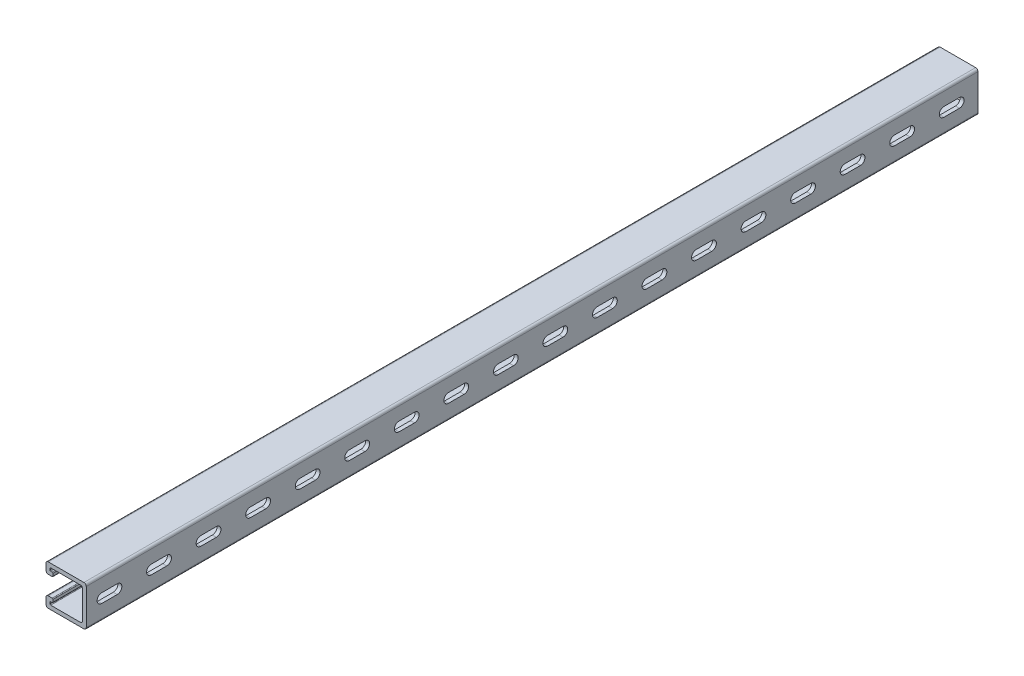
SolidWorks part; units mm, degrees
ref_plane "Front Plane" through (0, 0, 0) normal (0, 0, 1) x (1, 0, 0)
ref_plane "Top Plane" through (0, 0, 0) normal (0, 1, 0) x (1, 0, 0)
ref_plane "Right Plane" through (0, 0, 0) normal (1, 0, 0) x (0, 0, -1)
sketch "Sketch1" plane through (0, 0, 0) normal (0, 0, 1) x (1, 0, 0)
  line L0 (-13.5255, 9.525) -> (-18.2499, 9.525)
  line L1 (-20.6375, 11.9126) -> (-20.6375, 18.2499)
  line L2 (-18.2499, 20.6375) -> (18.2499, 20.6375)
  line L3 (20.6375, 18.2499) -> (20.6375, -18.2499)
  line L4 (18.2499, -20.6375) -> (-18.2499, -20.6375)
  line L5 (-20.6375, -18.2499) -> (-20.6375, -11.9126)
  line L6 (-18.2499, -9.525) -> (-13.5255, -9.525)
  line L7 (0, 0) -> (20.6375, 0) construction
  line L8 (0, 0) -> (0, 20.6375) construction
  arc A0 (-20.6375, 18.2499) -> (-18.2499, 20.6375) centre (-18.2499, 18.2499) cw
  arc A1 (-18.2499, 9.525) -> (-20.6375, 11.9126) centre (-18.2499, 11.9126) cw
  arc A2 (-20.6375, -11.9126) -> (-18.2499, -9.525) centre (-18.2499, -11.9126) cw
  arc A3 (-18.2499, -20.6375) -> (-20.6375, -18.2499) centre (-18.2499, -18.2499) cw
  arc A4 (20.6375, -18.2499) -> (18.2499, -20.6375) centre (18.2499, -18.2499) cw
  arc A5 (18.2499, 20.6375) -> (20.6375, 18.2499) centre (18.2499, 18.2499) cw
  point P14 (-20.6375, 20.6375)
  point P23 (20.6375, -20.6375)
  point P26 (20.6375, 20.6375)
  dimension "D4" = 2.3876
  dimension "D1" = 41.275
  dimension "D2" = 41.275
  dimension "D3" = 19.05
  dimension "D5" = 7.112
extrude "Extrude-Thin1" add sketch "Sketch1" against normal blind 914.4 thin thin type one direction wall 4.064
fillet "Fillet2" radius 0.762 8 edges at (-16.5735, 13.589, -457.2) (-16.5735, -16.5735, -457.2) (-16.5735, 16.5735, -457.2) (-13.5255, 13.589, -457.2) (-13.5255, 9.525, -457.2) (-13.5255, -9.525, -457.2) (-13.5255, -13.589, -457.2) (-16.5735, -13.589, -457.2)
fillet "Fillet3" radius 1.524 2 edges at (16.5735, 16.5735, -457.2) (16.5735, -16.5735, -457.2)
sketch "Sketch2" plane through (20.6375, 0, 0) normal (1, 0, 0) x (0, 0, -1)
  line L0 (15.875, 0) -> (31.75, 0) construction
  line L1 (15.875, 4.7625) -> (31.75, 4.7625)
  line L2 (15.875, -4.7625) -> (31.75, -4.7625)
  line L4 (15.875, 0) -> (0, 0) construction
  line L5 (23.8125, 0) -> (74.6125, 0) construction
  line L6 (0, 18.2499) -> (0, -18.2499) construction
  arc A0 (15.875, 4.7625) -> (15.875, -4.7625) centre (15.875, 0) ccw
  arc A1 (31.75, -4.7625) -> (31.75, 4.7625) centre (31.75, 0) ccw
  point P2 (23.8125, 0)
  dimension "D1" = 9.525
  dimension "D2" = 25.4
  dimension "Center Length" = 50.8
  dimension "D3" = 11.1125
extrude "Cut-Extrude1" cut sketch "Sketch2" against normal through all
pattern_linear "LPattern1" count 18 spacing 50.8 along (0, 0, -1) of "Cut-Extrude1"
sketch "Sketch3" plane through (0, 0, 0) normal (1, 0, 0) x (0, 0, -1)
  line L0 (0, 0) -> (914.4, 0) construction
  line L1 (914.4, 18.2499) -> (914.4, -18.2499) construction
  point P3 (101.6, 0)
  point P4 (812.8, 0)
  dimension "D1" = 101.6
  dimension "D2" = 101.6
equation "\"D3@LPattern1\" = \"Center Length@Sketch2\""
equation "\"D1@LPattern1\" = \"Length@Extrude-Thin1\"/\"Center Length@Sketch2\""
